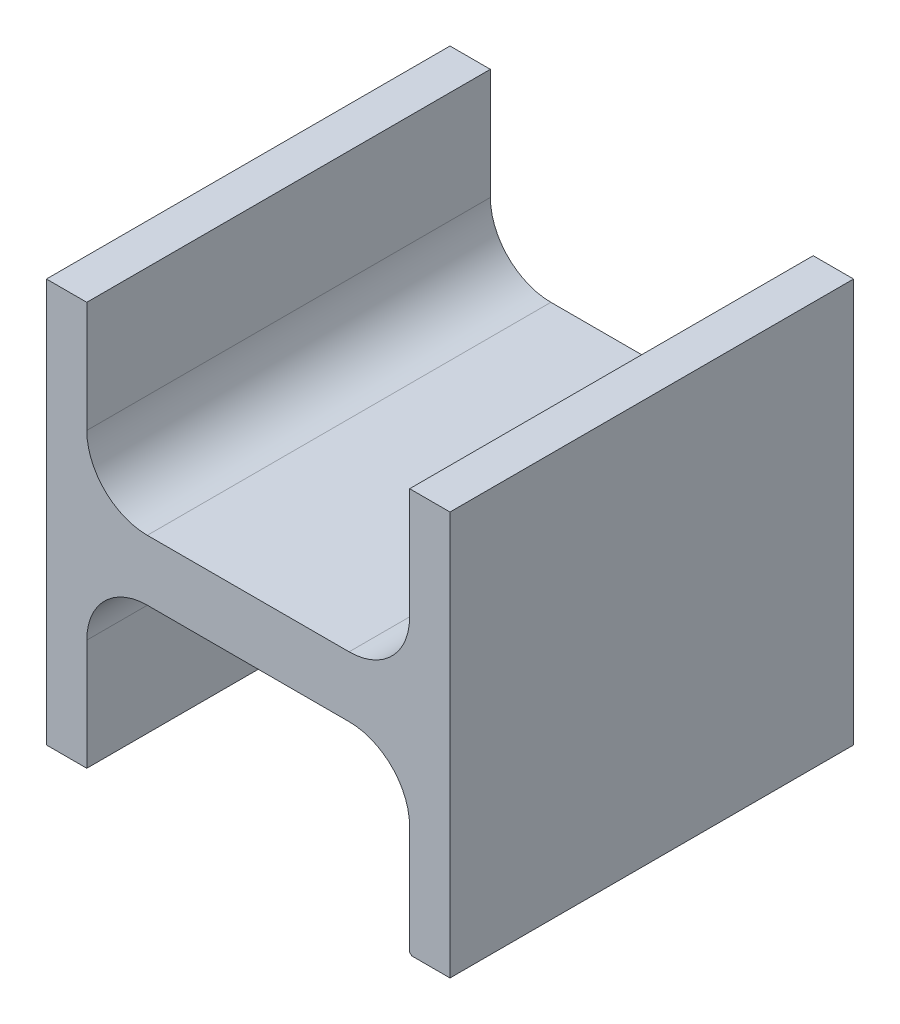
SolidWorks part; units mm, degrees
ref_plane "Front Plane" through (0, 0, 0) normal (0, 0, 1) x (1, 0, 0)
ref_plane "Top Plane" through (0, 0, 0) normal (0, 1, 0) x (1, 0, 0)
ref_plane "Right Plane" through (0, 0, 0) normal (1, 0, 0) x (0, 0, -1)
sketch "Sketch2" plane through (0, 0, 0) normal (0, 0, 1) x (1, 0, 0)
  line L0 (-10, -10) -> (-8, -10)
  line L2 (10, 10) -> (10, -10)
  line L4 (-10, 10) -> (-10, -10)
  line L5 (10, 10) -> (-10, -10) construction
  line L6 (10, -10) -> (-10, 10) construction
  line L7 (-8, -10) -> (-8, -1.5)
  line L8 (-8, -1.5) -> (8, -1.5)
  line L9 (8, -1.5) -> (8, -10)
  line L10 (8, -10) -> (10, -10)
  line L11 (-10, 10) -> (-8, 10)
  line L12 (-8, 10) -> (-8, 1.5)
  line L13 (-8, 1.5) -> (8, 1.5)
  line L14 (8, 1.5) -> (8, 10)
  line L15 (8, 10) -> (10, 10)
  point P0 (0, 0)
  point P6 (-8, -10)
  point P7 (8, -10)
  point P8 (-8, 10)
  point P9 (8, 10)
extrude "Boss-Extrude2" add sketch "Sketch2" along normal blind 20
fillet "Fillet1" radius 3 1 edges at (-8, 1.5, 10)
fillet "Fillet2" radius 3 3 edges at (-8, -1.5, 10) (8, -1.5, 10) (8, 1.5, 10)
sketch "Sketch3" plane through (0, 0, 20) normal (0, 0, 1) x (1, 0, 0)
  line L0 (8, -10) -> (8.1036, -10)
  line L1 (8, -10) -> (10, -10) construction
  line L2 (8.1036, -10) -> (8, -9.8964)
  line L3 (8, -4.5) -> (8, -10) construction
  line L4 (8, -9.8964) -> (8, -10)
extrude "Cut-Extrude1" cut sketch "Sketch3" against normal through all
